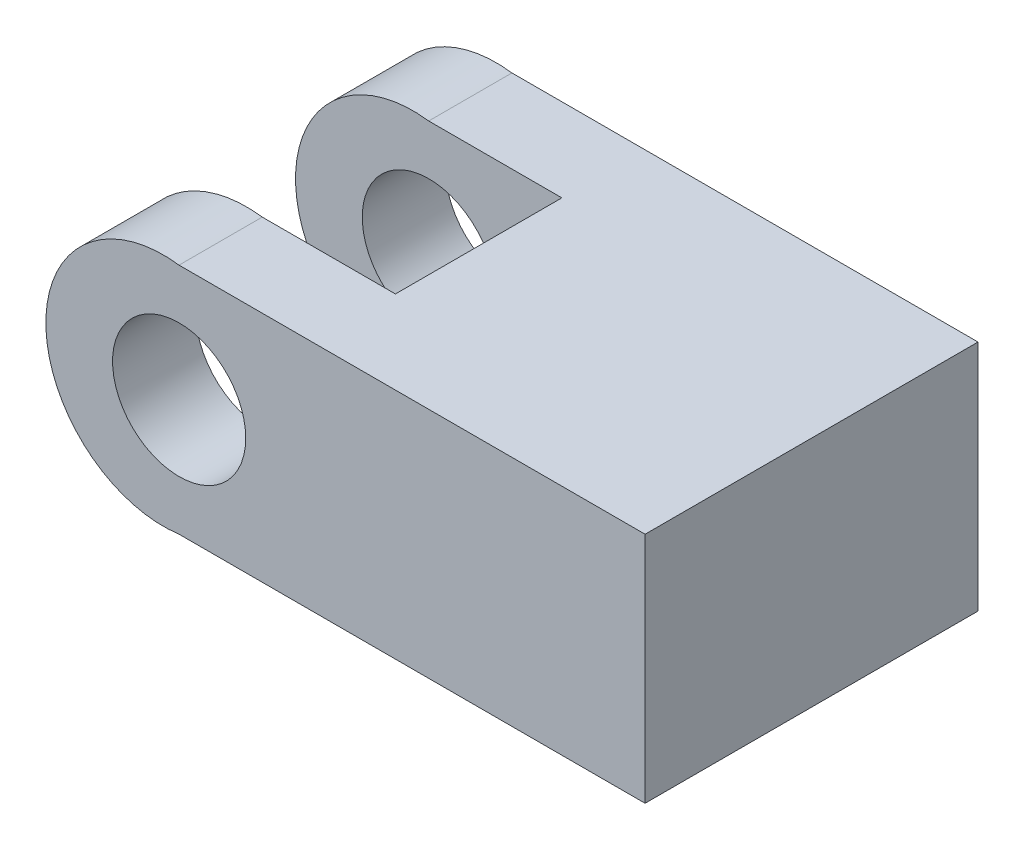
SolidWorks part; units mm, degrees
ref_plane "Plan de face" through (0, 0, 0) normal (0, 0, 1) x (1, 0, 0)
ref_plane "Plan de dessus" through (0, 0, 0) normal (0, 1, 0) x (1, 0, 0)
ref_plane "Plan de droite" through (0, 0, 0) normal (1, 0, 0) x (0, 0, -1)
sketch "Esquisse1" plane through (0, 0, 0) normal (0, 1, 0) x (1, 0, 0)
  line L1 (0, 0) -> (10, 0)
  line L2 (0, 0) -> (0, 10)
  line L3 (0, 10) -> (10, 10)
  line L4 (10, 0) -> (10, 10)
  dimension "D1" = 10
  dimension "D2" = 10
extrude "Boss.-Extru.1" add sketch "Esquisse1" along normal blind 7
sketch "Esquisse2" plane through (0, 0, 0) normal (0, 0, 1) x (1, 0, 0)
  line L1 (0, 7) -> (0, 0)
  line L4 (-4, 0) -> (0, 0)
  line L5 (0, 7) -> (-4, 7)
  arc A0 (-4, 0) -> (-4, 7) centre (-4.4688, 3.5) cw
extrude "Boss.-Extru.2" add sketch "Esquisse2" against normal blind 10
sketch "Esquisse3" plane through (0, 7, 0) normal (0, 1, 0) x (1, 0, 0)
  line L0 (0, 0) -> (0, 10) construction
  line L1 (10, 10) -> (-4, 10) construction
sketch "Esquisse6" plane through (0, 0, 0) normal (0, 0, 1) x (1, 0, 0)
  line L0 (-8, 7) -> (-8, 0) construction
  line L1 (-4, 0) -> (10, 0) construction
  circle A0 centre (-3.9963, 3.5) radius 2
  dimension "D2" = 4
  dimension "D1" = 4.0037
  dimension "D3" = 3.5
extrude "Enlèv. mat.-Extru.1" cut sketch "Esquisse6" against normal through all
sketch "Esquisse7" plane through (0, 7, 0) normal (0, 1, 0) x (1, 0, 0)
  line L0 (-4, 0) -> (10, 0) construction
  line L1 (0, 2.5) -> (-8.5341, 2.5)
  line L2 (0, 2.5) -> (0, 7.5)
  line L3 (0, 7.5) -> (-8.5341, 7.5)
  line L4 (-8.5341, 2.5) -> (-8.5341, 7.5)
  line L5 (10, 10) -> (-4, 10) construction
  dimension "D1" = 2.5
  dimension "D2" = 2.5
extrude "Enlèv. mat.-Extru.3" cut sketch "Esquisse7" against normal blind 10 and the other way blind 10
